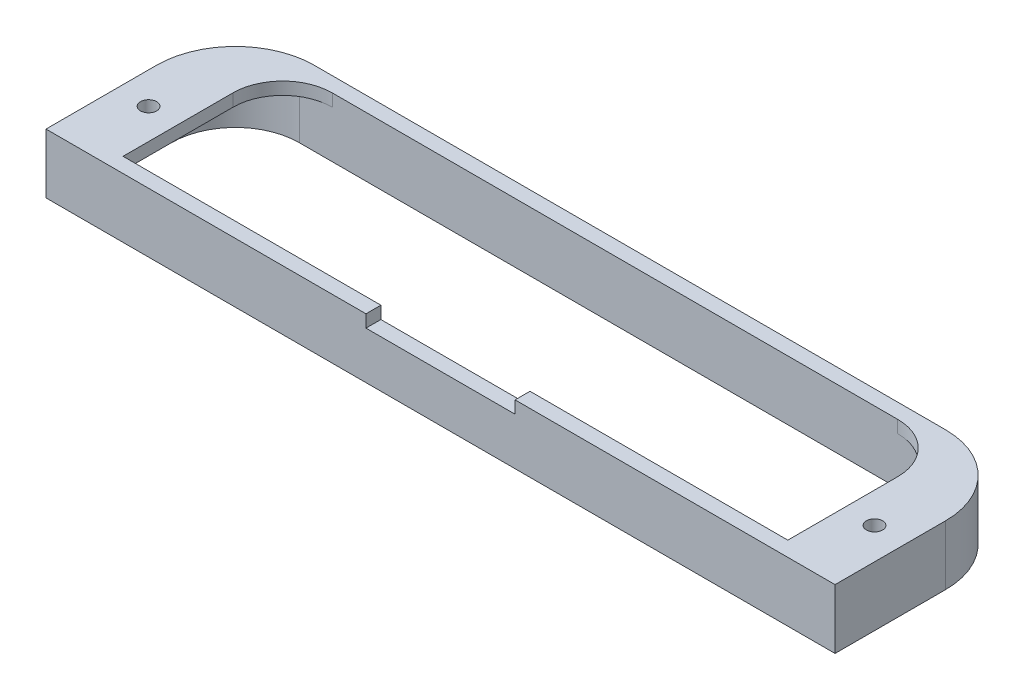
SolidWorks part; units mm, degrees
ref_plane "Front" through (0, 0, 0) normal (0, 0, 1) x (1, 0, 0)
ref_plane "Top" through (0, 0, 0) normal (0, 1, 0) x (1, 0, 0)
ref_plane "Right" through (0, 0, 0) normal (1, 0, 0) x (0, 0, -1)
ref_axis "X" through (-80.9, 0, 0) along (1, 0, 0)
ref_axis "Y" through (0, -50, 0) along (0, 1, 0)
ref_axis "Z" through (0, 0, -80.9) along (0, 0, 1)
sketch "Sketch1" plane through (0, 0, 0) normal (0, 1, 0) x (1, 0, 0)
  line L0 (-63.5, 0) -> (-53.5, 0)
  line L1 (-53.5, 2.4) -> (-53.5, 20.08)
  line L2 (-45.5, 28.08) -> (45.5, 28.08)
  line L3 (53.5, 20.08) -> (53.5, 2.4)
  line L4 (53.5, 0) -> (63.5, 0)
  line L5 (63.5, 0) -> (63.5, 17.78)
  line L6 (50.8, 30.48) -> (-50.8, 30.48)
  line L7 (-63.5, 17.78) -> (-63.5, 0)
  line L8 (-53.5, 0) -> (53.5, 0)
  line L9 (-53.5, 2.4) -> (53.5, 2.4)
  line L10 (-53.5, 0) -> (-53.5, 2.4) construction
  line L11 (53.5, 0) -> (53.5, 2.4) construction
  arc A0 (-53.5, 20.08) -> (-45.5, 28.08) centre (-45.5, 20.08) cw
  arc A1 (45.5, 28.08) -> (53.5, 20.08) centre (45.5, 20.08) cw
  arc A2 (63.5, 17.78) -> (50.8, 30.48) centre (50.8, 17.78) ccw
  arc A3 (-50.8, 30.48) -> (-63.5, 17.78) centre (-50.8, 17.78) ccw
  dimension "D5" = 12.7
  dimension "D6" = 8
  dimension "D1" = 127
  dimension "D2" = 10
  dimension "D3" = 2.4
  dimension "D4" = 30.48
  dimension "D7" = 2.4
extrude "Boss-Extrude1" add sketch "Sketch1" along normal blind 2
hole_wizard "M2 Clearance Hole1" positions "Sketch6" profile "Sketch7" hole size "M2" standard "ANSI Metric" end condition up to next
sketch "Sketch6" plane through (0, 2, 0) normal (0, 1, 0) x (1, 0, 0)
  line L0 (-58.42, 11.43) -> (58.42, 11.43) construction
  line L3 (0, 11.43) -> (0, 0) construction
  point P0 (-58.42, 11.43)
  point P2 (58.42, 11.43)
  dimension "D1" = 11.43
  dimension "D2" = 116.84
sketch "Sketch7" plane through (-58.42, 2, -11.43) normal (1, 0, 0) x (0, 0, 1)
  line L0 (0, 0) -> (0, 2)
  line L1 (0, 2) -> (1.3, 2)
  line L2 (1.3, 2) -> (1.3, 0)
  line L5 (1.3, 0) -> (0, 0)
  line L11 (0, -6.35) -> (0, 107.95) construction
  dimension "Thru Hole Dia." = 2.6
  dimension "Thru Hole Depth" = 2
sketch "Sketch8" plane through (0, 0, 0) normal (0, -1, 0) x (-1, 0, 0)
  line L0 (-61.1, 2.4) -> (61.1, 2.4)
  line L1 (61.1, 2.4) -> (61.1, 17.78)
  line L2 (50.8, 28.08) -> (-50.8, 28.08)
  line L3 (-61.1, 17.78) -> (-61.1, 2.4)
  line L4 (63.5, 0) -> (63.5, 17.78)
  line L5 (50.8, 30.48) -> (-50.8, 30.48)
  line L6 (-63.5, 17.78) -> (-63.5, 0)
  line L7 (-63.5, 0) -> (63.5, 0)
  line L8 (63.5, 0) -> (63.5, 17.78)
  line L9 (50.8, 30.48) -> (-50.8, 30.48)
  line L10 (-63.5, 17.78) -> (-63.5, 0)
  line L11 (-63.5, 0) -> (63.5, 0)
  arc A0 (61.1, 17.78) -> (50.8, 28.08) centre (50.8, 17.78) ccw
  arc A1 (-50.8, 28.08) -> (-61.1, 17.78) centre (-50.8, 17.78) ccw
  arc A2 (63.5, 17.78) -> (50.8, 30.48) centre (50.8, 17.78) ccw
  arc A3 (-50.8, 30.48) -> (-63.5, 17.78) centre (-50.8, 17.78) ccw
  arc A4 (63.5, 17.78) -> (50.8, 30.48) centre (50.8, 17.78) ccw
  arc A5 (-50.8, 30.48) -> (-63.5, 17.78) centre (-50.8, 17.78) ccw
  dimension "D1" = 0
  dimension "D2" = 2.4
extrude "Boss-Extrude2" add sketch "Sketch8" along normal blind 7.6
sketch "Sketch9" plane through (0, 2, 0) normal (0, 1, 0) x (1, 0, 0)
  line L0 (-12, 2.4) -> (-12, 0)
  line L1 (-53.5, 2.4) -> (53.5, 2.4) construction
  line L2 (-63.5, 0) -> (63.5, 0) construction
  line L3 (-12, 0) -> (12, 0)
  line L4 (12, 0) -> (12, 2.4)
  line L5 (12, 2.4) -> (-12, 2.4)
  line L6 (0, 0) -> (0, 2.4) construction
  dimension "D1" = 24
extrude "Cut-Extrude1" cut sketch "Sketch9" against normal blind 2
